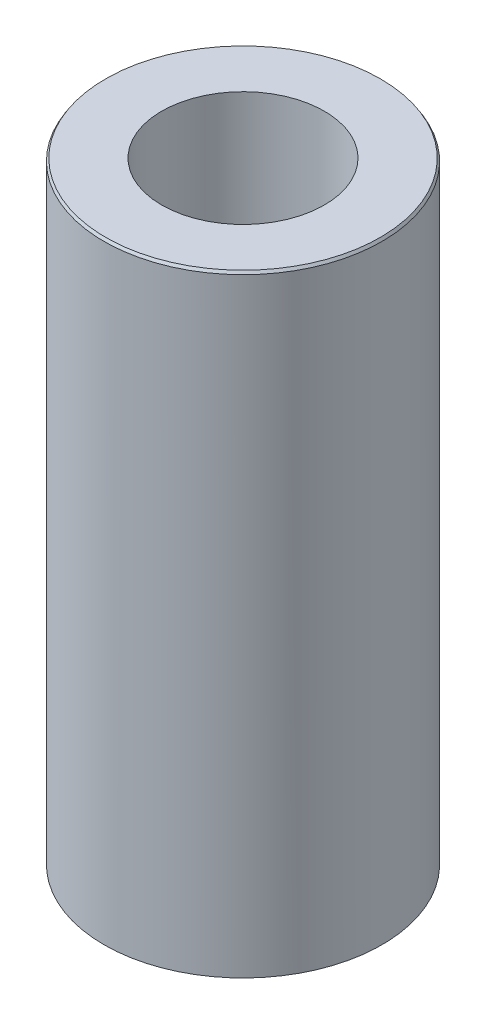
SolidWorks part; units mm, degrees
ref_plane "Front Plane" through (0, 0, 0) normal (0, 0, 1) x (1, 0, 0)
ref_plane "Top Plane" through (0, 0, 0) normal (0, 1, 0) x (1, 0, 0)
ref_plane "Right Plane" through (0, 0, 0) normal (1, 0, 0) x (0, 0, -1)
sketch "Sketch1" plane through (0, 0, 0) normal (0, 1, 0) x (1, 0, 0)
  circle A0 centre (0, 0) radius 12.5
  dimension "SHAFT_OD" = 25
extrude "Boss-Extrude1" add sketch "Sketch1" along normal blind 55.156
sketch "Sketch2" plane through (0, 0, 0) normal (0, 1, 0) x (1, 0, 0)
  circle A0 centre (0, 0) radius 7.3147
  dimension "BORE_D" = 14.6293
extrude "Cut-Extrude1" cut sketch "Sketch2" along normal through all
chamfer "Chamfer1" distance 0.2416 angle 31.897 2 edges at (0, 55.156, 12.5) (0, 0, 12.5) first distance on face at (0, 55.156, 12.5) first distance on face at (0, 0, 7.3147)
